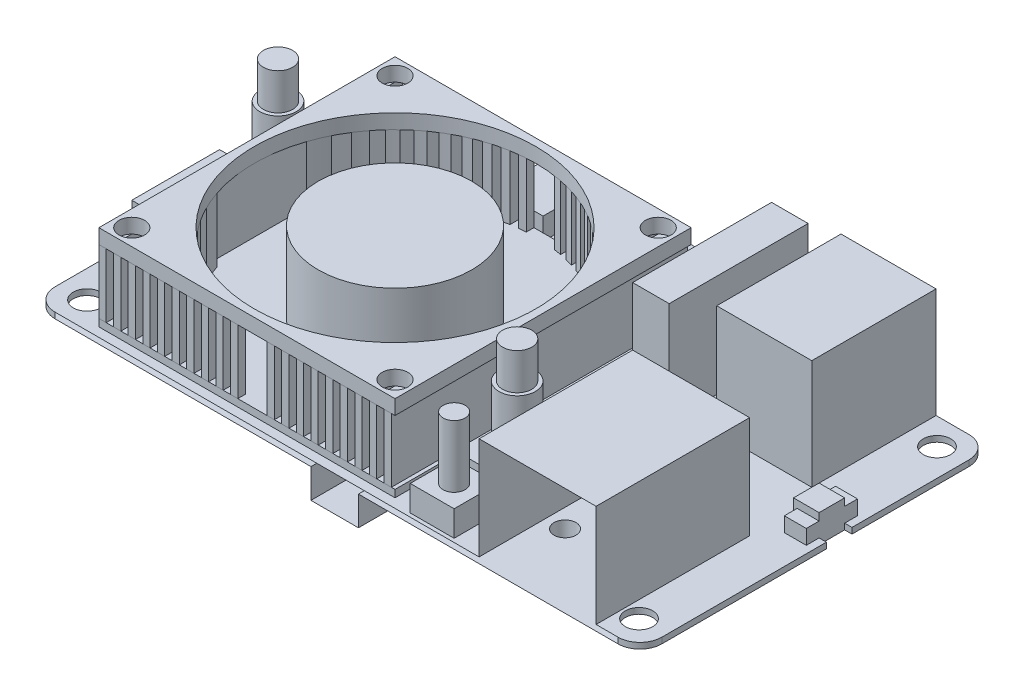
SolidWorks part; units mm, degrees
ref_plane "Front Plane" through (0, 0, 0) normal (0, 0, 1) x (1, 0, 0)
ref_plane "Top Plane" through (0, 0, 0) normal (0, 1, 0) x (1, 0, 0)
ref_plane "Right Plane" through (0, 0, 0) normal (1, 0, 0) x (0, 0, -1)
sketch "Sketch1" plane through (0, 0, 0) normal (0, 1, 0) x (1, 0, 0)
  line L0 (0, 0) -> (-83, 0)
  line L1 (-83, 0) -> (-83, 48)
  line L2 (-83, 48) -> (0, 48)
  line L3 (0, 48) -> (0, 0)
  line L4 (0, 24) -> (-83, 24) construction
  circle A0 centre (-79.25, 44.375) radius 1.875
  circle A1 centre (-79.25, 3.625) radius 1.875
  circle A2 centre (-3.75, 44.375) radius 1.875
  circle A3 centre (-3.75, 3.625) radius 1.875
  dimension "D1" = 20.375
  dimension "D2" = 20.375
  dimension "D3" = 3.75
  dimension "D4" = 3.75
extrude "Boss-Extrude1" add sketch "Sketch1" along normal blind 0.8
fillet "Fillet1" radius 3 4 edges at (-83, 0.4, -48) (0, 0.4, -48) (0, 0.4, 0) (-83, 0.4, 0)
sketch "Sketch2" plane through (0, 0.8, 0) normal (0, 1, 0) x (1, 0, 0)
  line L0 (-82.5, 13) -> (-77.4321, 13)
  line L1 (-77.4321, 13) -> (-77.4321, 25)
  line L2 (-77.4321, 25) -> (-82.5, 25)
  line L3 (-82.5, 25) -> (-82.5, 13)
  line L4 (-74, 40.5) -> (-74, 0)
  line L5 (-74, 0) -> (-33.5, 0)
  line L6 (-33.5, 0) -> (-33.5, 40.5)
  line L7 (-33.5, 40.5) -> (-74, 40.5)
  line L8 (-74, 20.25) -> (-53.75, 20.25) construction
  line L9 (-53.75, 20.25) -> (-53.75, 40.5) construction
  line L10 (-83, 45) -> (-83, 3) construction
  line L11 (-80, 0) -> (-3, 0) construction
  line L12 (-22, 0) -> (-22, 21)
  line L13 (-22, 21) -> (-6, 21)
  line L14 (-6, 21) -> (-6, 0)
  line L15 (-6, 0) -> (-22, 0)
  line L16 (-30, 48) -> (-30, 29)
  line L17 (-3, 48) -> (-80, 48) construction
  line L18 (-30, 29) -> (-25, 29)
  line L19 (-25, 29) -> (-25, 48)
  line L20 (-25, 48) -> (-30, 48)
  line L21 (-20.5, 48) -> (-20.5, 31)
  line L22 (-20.5, 31) -> (-7.5, 31)
  line L23 (-7.5, 31) -> (-7.5, 48)
  line L24 (-7.5, 48) -> (-20.5, 48)
  line L25 (0, 3) -> (0, 45) construction
  line L26 (-78.5, 32.5) -> (-74, 32.5)
  line L27 (-78.5, 25.5) -> (-74, 25.5)
  line L28 (-29, 15.7056) -> (-33.5, 15.7056)
  line L29 (-31.9171, 0.5) -> (-31.9171, 6.5)
  line L30 (-29, 8.7056) -> (-33.5, 8.7056)
  line L31 (-31.9171, 6.5) -> (-25.9171, 6.5)
  line L32 (-25.9171, 6.5) -> (-25.9171, 0.5)
  line L33 (-25.9171, 0.5) -> (-31.9171, 0.5)
  line L34 (-31.9171, 3.5) -> (-28.2034, 3.5) construction
  line L35 (-28.9171, 6.5) -> (-28.9171, 3.5) construction
  line L36 (-75.5, 43.75) -> (-68.5, 43.75)
  line L37 (-68.5, 43.75) -> (-68.5, 48.75)
  line L38 (-68.5, 48.75) -> (-75.5, 48.75)
  line L39 (-75.5, 48.75) -> (-75.5, 43.75)
  line L40 (-61.5, 41.75) -> (-61.5, 48.75)
  line L41 (-61.5, 48.75) -> (-55, 48.75)
  line L42 (-55, 48.75) -> (-55, 41.75)
  line L43 (-55, 41.75) -> (-61.5, 41.75)
  line L44 (-42, 48) -> (-42, 40.5)
  line L45 (-42, 40.5) -> (-37, 40.5)
  line L46 (-37, 40.5) -> (-37, 48)
  line L47 (-37, 48) -> (-42, 48)
  line L48 (0, 29) -> (-1, 29)
  line L49 (-1, 29) -> (-1, 25.5)
  line L50 (-1, 25.5) -> (0, 25.5)
  line L51 (-1, 29) -> (-1, 30.75)
  line L52 (-1, 30.75) -> (-4, 30.75)
  line L53 (-4, 30.75) -> (-4, 29)
  line L54 (-4, 29) -> (-4.5, 29)
  line L55 (-4.5, 29) -> (-4.5, 25.5)
  line L56 (-4.5, 25.5) -> (-4, 25.5)
  line L57 (-4, 25.5) -> (-4, 23.75)
  line L58 (-4, 23.75) -> (-1, 23.75)
  line L59 (-1, 23.75) -> (-1, 25.5)
  line L60 (-29, 27.25) -> (-29, 20.25)
  line L61 (-29, 20.25) -> (-27, 20.25)
  line L62 (-29, 27.25) -> (-27, 27.25)
  line L63 (-27, 27.25) -> (-27, 25.5)
  line L64 (-27, 25.5) -> (-26.5, 25.5)
  line L65 (-26.5, 25.5) -> (-26.5, 22)
  line L66 (-26.5, 22) -> (-27, 22)
  line L67 (-27, 22) -> (-27, 20.25)
  line L68 (-4, 29) -> (-1, 29)
  line L69 (-4, 25.5) -> (-1, 25.5)
  line L70 (-27, 25.5) -> (-29, 25.5)
  line L71 (-27, 22) -> (-29, 22)
  circle A0 centre (-53.75, 20.25) radius 19.25
  circle A1 centre (-71.75, 38.25) radius 1.75
  circle A2 centre (-35.75, 38.25) radius 1.75
  circle A3 centre (-35.75, 2.25) radius 1.75
  circle A4 centre (-71.75, 2.25) radius 1.75
  circle A5 centre (-53.75, 20.25) radius 10.5
  circle A6 centre (-78.5, 29) radius 2
  circle A7 centre (-28.9171, 3.5) radius 1.5
  circle A8 centre (-29, 12.2056) radius 2.5
  circle A9 centre (-78.5, 29) radius 2.5
  circle A10 centre (-78.5, 29) radius 3.5
  circle A11 centre (-29, 12.2056) radius 2
  circle A12 centre (-29, 12.2056) radius 3.5
  line M5 (-3, 48) -> (-80, 48)
  line M9 (-80, 0) -> (-3, 0)
  line M11 (0, 3) -> (0, 45)
  dimension "D1" = 9
  dimension "D3" = 2.25
  dimension "D5" = 6
  dimension "D17" = 4.5
  dimension "D18" = 0.5
  dimension "D19" = 6.5
  dimension "D35" = 1.75
  dimension "D2" = 0
  dimension "D4" = 2.25
  dimension "D6" = 16
  dimension "D7" = 21
  dimension "D8" = 13
  dimension "D9" = 5
  dimension "D10" = 4.5
  dimension "D11" = 7.5
  dimension "D12" = 0.5
  dimension "D13" = 13
  dimension "D14" = 12
  dimension "D15" = 4
  dimension "D16" = 4.5
  dimension "D20" = 7
  dimension "D21" = 0.75
  dimension "D22" = 0.75
  dimension "D23" = 1
  dimension "D24" = 3.5
  dimension "D25" = 19
  dimension "D26" = 17
  dimension "D27" = 19
  dimension "D28" = 7
  dimension "D29" = 5
  dimension "D30" = 13
  dimension "D31" = 7
  dimension "D32" = 7.5
  dimension "D33" = 7
  dimension "D34" = 5
  dimension "D36" = 2
  dimension "D37" = 3.5
  dimension "D38" = 1.75
  dimension "D39" = 0.5
extrude "Boss-Extrude2" add sketch "Sketch2" along normal blind 2 from offset 11 separate body contours L6 L7 L4 A0 M9 region at (-58, 0.8, -39.9272)
extrude "Boss-Extrude3" add sketch "Sketch2<3>" along normal blind 15 contours L22 L23 L21 M5 region at (-14, 0.8, -39.5)
sketch "Sketch2<3>" plane through (0, 0.8, 0) normal (0, 1, 0) x (1, 0, 0) same geometry as "Sketch2"
extrude "Boss-Extrude4" add sketch "Sketch2<4>" along normal blind 14 contours L14 L13 L12 M9 region at (-14, 0.8, -10.5)
sketch "Sketch2<4>" plane through (0, 0.8, 0) normal (0, 1, 0) x (1, 0, 0) same geometry as "Sketch2"
extrude "Boss-Extrude5" add sketch "Sketch2<5>" along normal blind 14 contours L18 L19 L16 M5 region at (-27.5, 0.8, -38.5)
sketch "Sketch2<5>" plane through (0, 0.8, 0) normal (0, 1, 0) x (1, 0, 0) same geometry as "Sketch2"
extrude "Boss-Extrude6" add sketch "Sketch2<6>" along normal blind 12 contours A7
sketch "Sketch2<6>" plane through (0, 0.8, 0) normal (0, 1, 0) x (1, 0, 0) same geometry as "Sketch2"
extrude "Boss-Extrude7" add sketch "Sketch2<7>" along normal blind 3.5 contours L33 L32 L31 L29 A7 region at (-31.8322, 0.8, -3.5)
sketch "Sketch2<7>" plane through (0, 0.8, 0) normal (0, 1, 0) x (1, 0, 0) same geometry as "Sketch2"
extrude "Boss-Extrude8" add sketch "Sketch2<8>" along normal blind 2.5 contours L39 L36 L37 M5 | L38 L39 L37 M5 region at (-72, 0.8, -45.875) region at (-72, 0.8, -48.375)
sketch "Sketch2<8>" plane through (0, 0.8, 0) normal (0, 1, 0) x (1, 0, 0) same geometry as "Sketch2"
extrude "Boss-Extrude9" add sketch "Sketch2<9>" along normal blind 3 contours L43 L42 L40 M5 | L42 L41 L40 M5 region at (-58.25, 0.8, -44.875) region at (-58.25, 0.8, -48.375)
sketch "Sketch2<9>" plane through (0, 0.8, 0) normal (0, 1, 0) x (1, 0, 0) same geometry as "Sketch2"
extrude "Boss-Extrude10" add sketch "Sketch2<10>" along normal blind 3.5 contours L7 L46 L44 M5 region at (-39.5, 0.8, -44.25)
sketch "Sketch2<10>" plane through (0, 0.8, 0) normal (0, 1, 0) x (1, 0, 0) same geometry as "Sketch2"
extrude "Boss-Extrude11" add sketch "Sketch2<11>" along normal blind 1 from offset 1.25 contours A10 L27 L4 L26 | A12 L28 L6 L30 | A10 | L7 L4 L5 L6 | A12 region at (-74.0832, 0.8, -29) region at (-31.25, 0.8, -15.6224)
sketch "Sketch2<11>" plane through (0, 0.8, 0) normal (0, 1, 0) x (1, 0, 0) same geometry as "Sketch2"
extrude "Boss-Extrude12" add sketch "Sketch2<12>" along normal blind 9 from surface contours A9 A6 | A8 A11 region at (-31.4293, 0.8, -12.2056) region at (-80.9293, 0.8, -29) starting at face at (-51.7143, 3.05, -23.3445)
sketch "Sketch2<12>" plane through (0, 0.8, 0) normal (0, 1, 0) x (1, 0, 0) same geometry as "Sketch2"
extrude "Boss-Extrude14" add sketch "Sketch2<13>" along normal blind 14 from offset 2.25 contours A6 | A11 region at (-78.5, 0.8, -29) region at (-29, 0.8, -12.2056)
sketch "Sketch2<13>" plane through (0, 0.8, 0) normal (0, 1, 0) x (1, 0, 0) same geometry as "Sketch2"
extrude "Boss-Extrude15" add sketch "Sketch2<14>" along normal blind 3 contours L58 L59 L49 L51 L52 L53 L54 L55 L56 L57 region at (-2.75, 0.8, -27.25)
sketch "Sketch2<14>" plane through (0, 0.8, 0) normal (0, 1, 0) x (1, 0, 0) same geometry as "Sketch2"
extrude "Cut-Extrude1" cut sketch "Sketch2<15>" against normal blind 3 contours L49 L50 L48 M11 region at (-0.5, 0.8, -27.25)
sketch "Sketch2<15>" plane through (0, 0.8, 0) normal (0, 1, 0) x (1, 0, 0) same geometry as "Sketch2"
extrude "Boss-Extrude16" add sketch "Sketch2<16>" along normal blind 2 contours L53 L68 L51 L52 | L69 L57 L58 L59 region at (-2.5, 0.8, -29.875) region at (-2.5, 0.8, -24.625)
sketch "Sketch2<16>" plane through (0, 0.8, 0) normal (0, 1, 0) x (1, 0, 0) same geometry as "Sketch2"
extrude "Boss-Extrude17" add sketch "Sketch2<17>" along normal blind 2 contours L67 L66 L65 L64 L63 L62 L60 L61 | L67 L71 L60 L61 | L70 L63 L62 L60 region at (-28, 0.8, -26.375) region at (-27.75, 0.8, -23.75) region at (-28, 0.8, -21.125)
sketch "Sketch2<17>" plane through (0, 0.8, 0) normal (0, 1, 0) x (1, 0, 0) same geometry as "Sketch2"
extrude "Boss-Extrude18" add sketch "Sketch2<18>" along normal blind 6 contours L71 L66 L65 L64 L70 L60 region at (-27.75, 0.8, -23.75)
sketch "Sketch2<18>" plane through (0, 0.8, 0) normal (0, 1, 0) x (1, 0, 0) same geometry as "Sketch2"
extrude "Boss-Extrude19" add sketch "Sketch2<19>" along normal blind 5.5 contours L2 L3 L0 L1 region at (-79.9661, 0.8, -19)
sketch "Sketch2<19>" plane through (0, 0.8, 0) normal (0, 1, 0) x (1, 0, 0) same geometry as "Sketch2"
chamfer "Chamfer1" distance 1 angle 45 1 edges at (-77.4321, 3.55, -25)
sketch "Sketch3" plane through (0, 3.05, 0) normal (0, 1, 0) x (1, 0, 0)
  line L0 (-74, 32.5) -> (-74, 25.5)
  line L1 (-73, 40.5) -> (-73, 32.5)
  line L2 (-73, 32.5) -> (-73, 25.5)
  line L3 (-73, 25.5) -> (-73, 0)
  line L4 (-72, 40.5) -> (-72, 32.5)
  line L5 (-72, 32.5) -> (-72, 25.5)
  line L6 (-72, 25.5) -> (-72, 0)
  line L7 (-71, 40.5) -> (-71, 32.5)
  line L8 (-71, 32.5) -> (-71, 25.5)
  line L9 (-71, 25.5) -> (-71, 0)
  line L10 (-70, 40.5) -> (-70, 32.5)
  line L11 (-70, 32.5) -> (-70, 25.5)
  line L12 (-74, 32.5) -> (-78.5, 32.5)
  line L13 (-78.5, 25.5) -> (-74, 25.5)
  line L14 (-74, 25.5) -> (-74, 0)
  line L15 (-74, 0) -> (-33.5, 0)
  line L16 (-33.5, 0) -> (-33.5, 8.7056)
  line L17 (-33.5, 8.7056) -> (-29, 8.7056)
  line L18 (-29, 15.7056) -> (-33.5, 15.7056)
  line L19 (-33.5, 15.7056) -> (-33.5, 40.5)
  line L20 (-33.5, 40.5) -> (-37, 40.5)
  line L21 (-37, 40.5) -> (-42, 40.5)
  line L22 (-42, 40.5) -> (-74, 40.5)
  line L23 (-74, 40.5) -> (-74, 32.5)
  line L24 (-74, 32.5) -> (-78.5, 32.5)
  line L25 (-78.5, 25.5) -> (-74, 25.5)
  line L26 (-74, 25.5) -> (-74, 0)
  line L27 (-74, 0) -> (-33.5, 0)
  line L28 (-33.5, 0) -> (-33.5, 8.7056)
  line L29 (-33.5, 8.7056) -> (-29, 8.7056)
  line L30 (-29, 15.7056) -> (-33.5, 15.7056)
  line L31 (-33.5, 15.7056) -> (-33.5, 40.5)
  line L32 (-33.5, 40.5) -> (-37, 40.5)
  line L33 (-37, 40.5) -> (-42, 40.5)
  line L34 (-42, 40.5) -> (-74, 40.5)
  line L35 (-74, 40.5) -> (-74, 32.5)
  line L36 (-70, 25.5) -> (-70, 0)
  line L37 (-69, 40.5) -> (-69, 32.5)
  line L38 (-69, 32.5) -> (-69, 25.5)
  line L39 (-69, 25.5) -> (-69, 0)
  line L40 (-68, 40.5) -> (-68, 32.5)
  line L41 (-68, 32.5) -> (-68, 25.5)
  line L42 (-68, 25.5) -> (-68, 0)
  line L43 (-67, 40.5) -> (-67, 32.5)
  line L44 (-67, 32.5) -> (-67, 25.5)
  line L45 (-67, 25.5) -> (-67, 0)
  line L46 (-66, 40.5) -> (-66, 32.5)
  line L47 (-66, 32.5) -> (-66, 25.5)
  line L48 (-66, 25.5) -> (-66, 0)
  line L49 (-65, 40.5) -> (-65, 32.5)
  line L50 (-65, 32.5) -> (-65, 25.5)
  line L51 (-65, 25.5) -> (-65, 0)
  line L52 (-64, 40.5) -> (-64, 32.5)
  line L53 (-64, 32.5) -> (-64, 25.5)
  line L54 (-64, 25.5) -> (-64, 0)
  line L55 (-63, 40.5) -> (-63, 32.5)
  line L56 (-63, 32.5) -> (-63, 25.5)
  line L57 (-63, 25.5) -> (-63, 0)
  line L58 (-62, 40.5) -> (-62, 32.5)
  line L59 (-62, 32.5) -> (-62, 25.5)
  line L60 (-62, 25.5) -> (-62, 0)
  line L61 (-61, 40.5) -> (-61, 32.5)
  line L62 (-61, 32.5) -> (-61, 25.5)
  line L63 (-61, 25.5) -> (-61, 0)
  line L64 (-60, 40.5) -> (-60, 32.5)
  line L65 (-60, 32.5) -> (-60, 25.5)
  line L66 (-60, 25.5) -> (-60, 0)
  line L67 (-59, 40.5) -> (-59, 32.5)
  line L68 (-59, 32.5) -> (-59, 25.5)
  line L69 (-59, 25.5) -> (-59, 0)
  line L70 (-58, 40.5) -> (-58, 32.5)
  line L71 (-58, 32.5) -> (-58, 25.5)
  line L72 (-58, 25.5) -> (-58, 0)
  line L73 (-57, 40.5) -> (-57, 32.5)
  line L74 (-57, 32.5) -> (-57, 25.5)
  line L75 (-57, 25.5) -> (-57, 0)
  line L76 (-56, 40.5) -> (-56, 32.5)
  line L77 (-56, 32.5) -> (-56, 25.5)
  line L78 (-56, 25.5) -> (-56, 0)
  line L79 (-55, 40.5) -> (-55, 32.5)
  line L80 (-55, 32.5) -> (-55, 25.5)
  line L81 (-55, 25.5) -> (-55, 0)
  line L82 (-54, 40.5) -> (-54, 32.5)
  line L83 (-54, 32.5) -> (-54, 25.5)
  line L84 (-54, 25.5) -> (-54, 0)
  line L85 (-53, 40.5) -> (-53, 32.5)
  line L86 (-53, 32.5) -> (-53, 25.5)
  line L87 (-53, 25.5) -> (-53, 0)
  line L88 (-52, 40.5) -> (-52, 32.5)
  line L89 (-52, 32.5) -> (-52, 25.5)
  line L90 (-52, 25.5) -> (-52, 0)
  line L91 (-51, 40.5) -> (-51, 32.5)
  line L92 (-51, 32.5) -> (-51, 25.5)
  line L93 (-51, 25.5) -> (-51, 0)
  line L94 (-50, 40.5) -> (-50, 32.5)
  line L95 (-50, 32.5) -> (-50, 25.5)
  line L96 (-50, 25.5) -> (-50, 0)
  line L97 (-49, 40.5) -> (-49, 32.5)
  line L98 (-49, 32.5) -> (-49, 25.5)
  line L99 (-49, 25.5) -> (-49, 0)
  line L100 (-48, 40.5) -> (-48, 32.5)
  line L101 (-48, 32.5) -> (-48, 25.5)
  line L102 (-48, 25.5) -> (-48, 0)
  line L103 (-47, 40.5) -> (-47, 32.5)
  line L104 (-47, 32.5) -> (-47, 25.5)
  line L105 (-47, 25.5) -> (-47, 0)
  line L106 (-46, 40.5) -> (-46, 32.5)
  line L107 (-46, 32.5) -> (-46, 25.5)
  line L108 (-46, 25.5) -> (-46, 0)
  line L109 (-45, 40.5) -> (-45, 32.5)
  line L110 (-45, 32.5) -> (-45, 25.5)
  line L111 (-45, 25.5) -> (-45, 0)
  line L112 (-44, 40.5) -> (-44, 32.5)
  line L113 (-44, 32.5) -> (-44, 25.5)
  line L114 (-44, 25.5) -> (-44, 0)
  line L115 (-43, 40.5) -> (-43, 32.5)
  line L116 (-43, 32.5) -> (-43, 25.5)
  line L117 (-43, 25.5) -> (-43, 0)
  line L118 (-42, 40.5) -> (-42, 32.5)
  line L119 (-42, 32.5) -> (-42, 25.5)
  line L120 (-42, 25.5) -> (-42, 0)
  line L121 (-41, 40.5) -> (-41, 32.5)
  line L122 (-41, 32.5) -> (-41, 25.5)
  line L123 (-41, 25.5) -> (-41, 0)
  line L124 (-40, 40.5) -> (-40, 32.5)
  line L125 (-40, 32.5) -> (-40, 25.5)
  line L126 (-40, 25.5) -> (-40, 0)
  line L127 (-39, 40.5) -> (-39, 32.5)
  line L128 (-39, 32.5) -> (-39, 25.5)
  line L129 (-39, 25.5) -> (-39, 0)
  line L130 (-38, 40.5) -> (-38, 32.5)
  line L131 (-38, 32.5) -> (-38, 25.5)
  line L132 (-38, 25.5) -> (-38, 0)
  line L133 (-37, 40.5) -> (-37, 32.5)
  line L134 (-37, 32.5) -> (-37, 25.5)
  line L135 (-37, 25.5) -> (-37, 0)
  line L136 (-36, 40.5) -> (-36, 32.5)
  line L137 (-36, 32.5) -> (-36, 25.5)
  line L138 (-36, 25.5) -> (-36, 0)
  line L139 (-35, 40.5) -> (-35, 32.5)
  line L140 (-35, 32.5) -> (-35, 25.5)
  line L141 (-35, 25.5) -> (-35, 0)
  line L142 (-34, 40.5) -> (-34, 32.5)
  line L143 (-34, 32.5) -> (-34, 25.5)
  line L144 (-34, 25.5) -> (-34, 0)
  circle A0 centre (-53.75, 20.25) radius 19.25 construction
  circle A1 centre (-53.75, 20.25) radius 19.25
  arc A2 (-78.5, 32.5) -> (-78.5, 25.5) centre (-78.5, 29) ccw
  arc A3 (-29, 8.7056) -> (-29, 15.7056) centre (-29, 12.2056) ccw
  arc A4 (-78.5, 32.5) -> (-78.5, 25.5) centre (-78.5, 29) ccw
  arc A5 (-29, 8.7056) -> (-29, 15.7056) centre (-29, 12.2056) ccw
  line M139 (-74, 25.5) -> (-74, 0)
  line M140 (-74, 0) -> (-33.5, 0)
  line M148 (-42, 40.5) -> (-74, 40.5)
  line M149 (-74, 40.5) -> (-74, 32.5)
  dimension "D2" = 41
  dimension "D1" = 0
extrude "Boss-Extrude23" add sketch "Sketch3" along normal blind 8.75 separate body contours L3 L2 L1 L0 M148 M149 M139 M140 | A1 L6 L9 M140 | A1 L36 L27 L39 | A1 L42 L27 L45 | A1 L48 L27 L51 | A1 L54 L27 L57 | A1 L60 L27 L63 | A1 L66 L27 L69 | A1 L72 L27 L75 | A1 L78 L27 L81 | A1 L8 L7 L4 L5 M148 | A1 L38 L37 L34 L10 L11 | A1 L43 L34 L40 | A1 L49 L34 L46 | A1 L55 L34 L52 | A1 L61 L34 L58 | A1 L67 L34 L64 | A1 L73 L34 L70 | A1 L79 L34 L76 | A1 L93 L96 M140 | A1 L99 L102 M140 | A1 L105 L108 M140 | A1 L111 L114 M140 | A1 L117 L120 M140 | A1 L123 L126 M140 | A1 L129 L132 M140 | A1 L135 L138 M140 | A1 L141 L144 L143 L142 L32 L139 L140 M140 | A1 L137 L136 L32 L133 L134 | A1 L131 L130 L33 L127 | A1 L124 L33 L121 | A1 L118 L115 M148 | A1 L112 L34 L109 | A1 L106 L34 L103 | A1 L100 L34 L97 | A1 L94 L34 L91 region at (-73.5, 3.05, -20.25) region at (-71.5156, 3.05, -34.062) region at (-71.5156, 3.05, -6.438) region at (-69.5129, 3.05, -35.8941) region at (-69.5129, 3.05, -4.6059) region at (-67.5125, 3.05, -37.1015) region at (-67.5125, 3.05, -3.3985) region at (-65.5128, 3.05, -37.9918) region at (-65.5128, 3.05, -2.5082) region at (-63.5134, 3.05, -38.6685) region at (-63.5134, 3.05, -1.8315) region at (-61.5139, 3.05, -39.181) region at (-61.5139, 3.05, -1.319) region at (-59.5139, 3.05, -39.5572) region at (-59.5139, 3.05, -0.9428) region at (-57.5121, 3.05, -39.8133) region at (-57.5121, 3.05, -0.6867) region at (-55.507, 3.05, -39.9587) region at (-55.507, 3.05, -0.5413) region at (-50.4888, 3.05, -39.8597) region at (-50.4888, 3.05, -0.6403) region at (-48.4864, 3.05, -39.632) region at (-48.4864, 3.05, -0.868) region at (-46.486, 3.05, -39.2871) region at (-46.486, 3.05, -1.2129) region at (-44.4865, 3.05, -38.8107) region at (-44.4865, 3.05, -1.6893) region at (-42.487, 3.05, -38.1786) region at (-42.487, 3.05, -2.3214) region at (-40.4874, 3.05, -37.3483) region at (-40.4874, 3.05, -3.1517) region at (-38.4873, 3.05, -36.2356) region at (-38.4873, 3.05, -4.2644) region at (-36.4856, 3.05, -34.6198) region at (-36.4856, 3.05, -5.8802) region at (-34.4768, 3.05, -20.25)
extrude "Boss-Extrude24" add sketch "Sketch2<20>" along normal blind 11 from surface contours A5 region at (-53.75, 0.8, -20.25) starting at face at (-51.7143, 3.05, -23.3445)
sketch "Sketch2<20>" plane through (0, 0.8, 0) normal (0, 1, 0) x (1, 0, 0) same geometry as "Sketch2"
sketch "Sketch4" plane through (0, 0, 0) normal (0, -1, 0) x (1, 0, 0)
  line L0 (-82.5, -41) -> (-78, -41)
  line L1 (-78, -41) -> (-78, -32.5)
  line L2 (-78, -32.5) -> (-82.5, -32.5)
  line L3 (-82.5, -32.5) -> (-82.5, -41)
  line L4 (-74.5, -10) -> (-74.5, -15)
  line L5 (-74.5, -15) -> (-63.5, -15)
  line L6 (-63.5, -15) -> (-63.5, -10)
  line L7 (-63.5, -10) -> (-74.5, -10)
  line L8 (-63, -2) -> (-63, -20)
  line L9 (-63, -20) -> (-50, -20)
  line L10 (-50, -20) -> (-50, -2)
  line L11 (-50, -2) -> (-63, -2)
  line L12 (-62, -3.5) -> (-62, -16.5)
  line L13 (-62, -16.5) -> (-51, -16.5)
  line L14 (-51, -16.5) -> (-51, -3.5)
  line L15 (-51, -3.5) -> (-62, -3.5)
  line L16 (-45, -13) -> (-45, 0)
  line L17 (-45, 0) -> (-38.5, 0)
  line L18 (-80, 0) -> (-3, 0) construction
  line L19 (-38.5, 0) -> (-38.5, -13)
  line L20 (-45, -13) -> (-38.5, -13)
  line L21 (-83, -45) -> (-83, -3) construction
  line L22 (-3, -48) -> (-80, -48) construction
  line L23 (-6, -21) -> (-6, 0) construction
  line L24 (-6, -21) -> (-6, 0)
  line L25 (-22, 0) -> (-22, -21) construction
  line L26 (-22, 0) -> (-22, -21)
  circle A0 centre (-20.25, -10) radius 1.5
  circle A1 centre (-7.75, -10) radius 1.5
  circle A2 centre (-29, -12.2056) radius 2 construction
  circle A3 centre (-78.5, -29) radius 2 construction
  circle A4 centre (-29, -12.2056) radius 2
  circle A5 centre (-78.5, -29) radius 2
  circle A6 centre (-78.5, -29) radius 1.5
  circle A7 centre (-29, -12.2056) radius 1.5
  line M6 (-3, 0) -> (-80, 0)
  dimension "D1" = 8.5
  dimension "D5" = 20
  dimension "D2" = 0.5
  dimension "D3" = 4.5
  dimension "D4" = 7
  dimension "D6" = 1
  dimension "D7" = 1
  dimension "D8" = 13
  dimension "D9" = 2
  dimension "D10" = 1.5
  dimension "D11" = 3.5
  dimension "D12" = 13
  dimension "D13" = 0.5
  dimension "D14" = 11
  dimension "D15" = 5
  dimension "D16" = 10
  dimension "D17" = 5
  dimension "D18" = 6.5
  dimension "D19" = 13
  dimension "D20" = 1.75
  dimension "D21" = 1.75
  dimension "D22" = 10
  dimension "D23" = 10
extrude "Boss-Extrude25" add sketch "Sketch4" along normal blind 4.5 contours L2 L3 L0 L1 region at (-80.25, 0, -36.75)
extrude "Boss-Extrude26" add sketch "Sketch4<3>" along normal blind 3 contours L6 L7 L4 L5 region at (-69, 0, -12.5)
sketch "Sketch4<3>" plane through (0, 0, 0) normal (0, -1, 0) x (1, 0, 0) same geometry as "Sketch4"
extrude "Boss-Extrude27" add sketch "Sketch4<4>" along normal blind 2.5 contours L14 L15 L12 L13 region at (-56.5, 0, -10)
sketch "Sketch4<4>" plane through (0, 0, 0) normal (0, -1, 0) x (1, 0, 0) same geometry as "Sketch4"
extrude "Boss-Extrude28" add sketch "Sketch4<5>" along normal blind 2 contours L10 L11 L8 L9 L15 L14 L13 L12 region at (-56.5, 0, -2.222)
sketch "Sketch4<5>" plane through (0, 0, 0) normal (0, -1, 0) x (1, 0, 0) same geometry as "Sketch4"
extrude "Boss-Extrude29" add sketch "Sketch4<6>" along normal blind 4 contours L16 L20 L19 M6 region at (-41.75, 0, -6.5)
sketch "Sketch4<6>" plane through (0, 0, 0) normal (0, -1, 0) x (1, 0, 0) same geometry as "Sketch4"
extrude "Boss-Extrude30" add sketch "Sketch4<7>" along normal blind 4 draft 5 contours A6 | A7 region at (-78.5, 0, -29) region at (-29, 0, -12.2056)
sketch "Sketch4<7>" plane through (0, 0, 0) normal (0, -1, 0) x (1, 0, 0) same geometry as "Sketch4"
extrude "Boss-Extrude31" add sketch "Sketch4<8>" along normal blind 2 draft 5 contours A0 | A1 region at (-20.25, 0, -10) region at (-7.75, 0, -10)
sketch "Sketch4<8>" plane through (0, 0, 0) normal (0, -1, 0) x (1, 0, 0) same geometry as "Sketch4"
